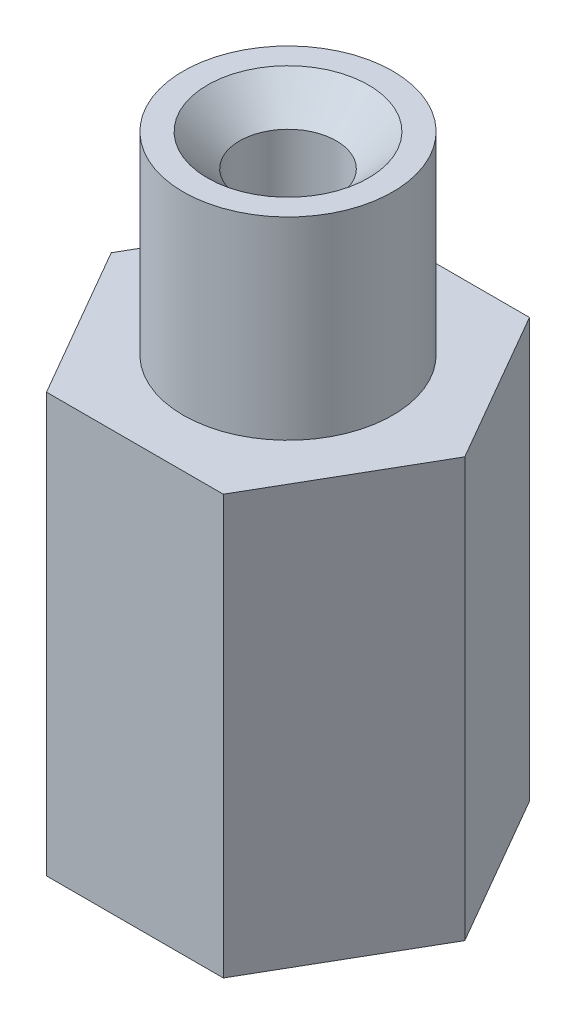
SolidWorks part; units mm, degrees
ref_plane "Front Plane" through (0, 0, 0) normal (0, 0, 1) x (1, 0, 0)
ref_plane "Top Plane" through (0, 0, 0) normal (0, 1, 0) x (1, 0, 0)
ref_plane "Right Plane" through (0, 0, 0) normal (1, 0, 0) x (0, 0, -1)
sketch "Szkic1" plane through (0, 0, 0) normal (0, 1, 0) x (1, 0, 0)
  line L1 (-10.9697, 0) -> (-5.4848, -9.5)
  line L2 (-5.4848, -9.5) -> (5.4848, -9.5)
  line L3 (5.4848, -9.5) -> (10.9697, 0)
  line L4 (10.9697, 0) -> (5.4848, 9.5)
  line L5 (5.4848, 9.5) -> (-5.4848, 9.5)
  line L6 (-5.4848, 9.5) -> (-10.9697, 0)
  circle A0 centre (0, 0) radius 9.5 construction
  circle A1 centre (0, 0) radius 6.5
  circle A2 centre (0, 0) radius 3
  dimension "D2" = 13
  dimension "D3" = 6
  dimension "D1" = 19
extrude "Dodanie-wyciągnięcie1" add sketch "Szkic1" along normal blind 9 and the other way blind 17 contours L5 L6 L1 L2 L3 L4 A1 | A1 A2 region at (-7.9759, 0, -4.6049) region at (-6.3162, 0, 0)
extrude "Dodanie-wyciągnięcie2" add sketch "Szkic1<3>" along normal blind 21 contours A1 A2 region at (-6.3162, 0, 0)
sketch "Szkic1<3>" plane through (0, 0, 0) normal (0, 1, 0) x (1, 0, 0) same geometry as "Szkic1"
chamfer "Sfazowanie1" distance 2 angle 45 1 edges at (0, 21, 3)
chamfer "Sfazowanie2" distance 4 angle 45 1 edges at (0, -17, 3)
sketch "Szkic3" plane through (0, -17, 0) normal (0, -1, 0) x (1, 0, 0)
  circle A0 centre (0, 0) radius 6
  dimension "D1" = 12
extrude "Wytnij-wyciągnięcie1" cut sketch "Szkic3" against normal blind 4
chamfer "Sfazowanie3" distance 1.5 angle 45 1 edges at (0, -13, -3)
